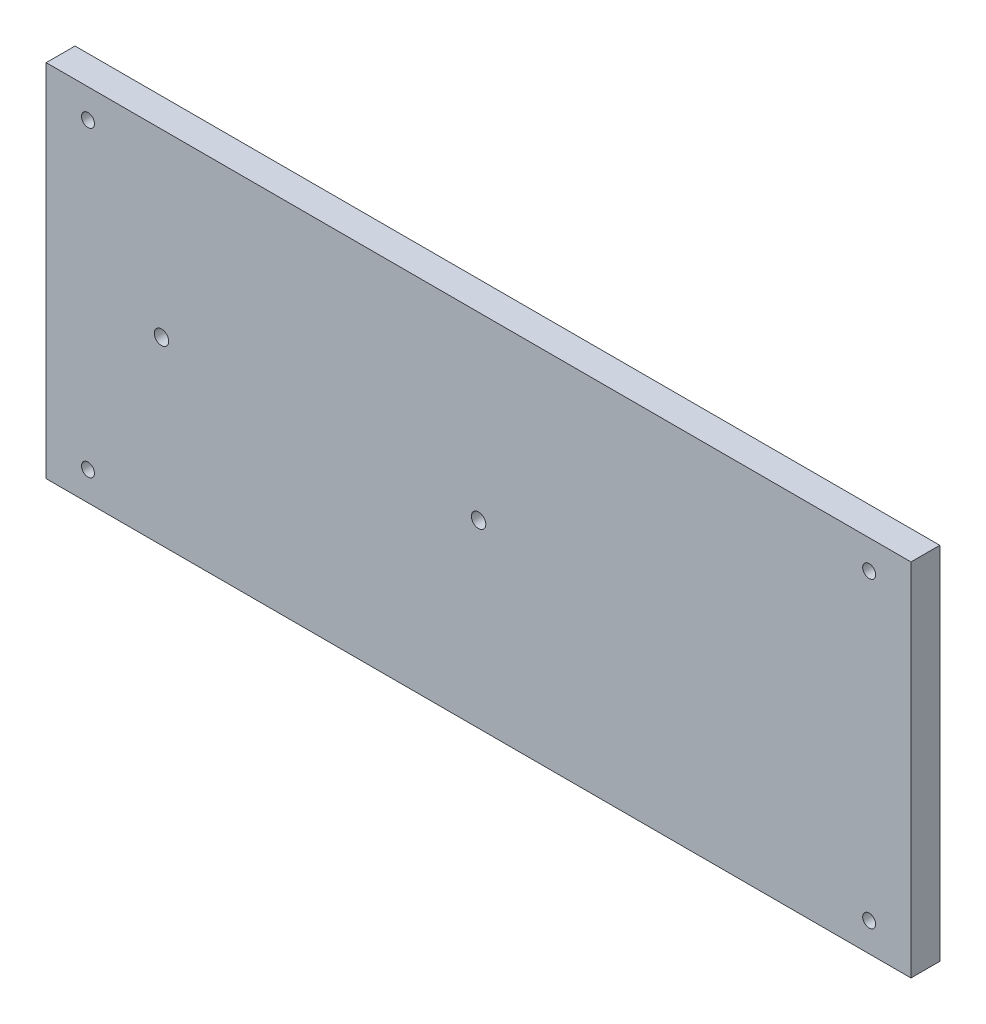
SolidWorks part; units mm, degrees
ref_plane "Plan de face" through (0, 0, 0) normal (0, 0, 1) x (1, 0, 0)
ref_plane "Plan de dessus" through (0, 0, 0) normal (0, 1, 0) x (1, 0, 0)
ref_plane "Plan de droite" through (0, 0, 0) normal (1, 0, 0) x (0, 0, -1)
sketch "Esquisse1" plane through (0, 0, 0) normal (0, 0, 1) x (1, 0, 0)
  line L1 (-122.4446, 41.9355) -> (177.5554, 41.9355)
  line L2 (-122.4446, 41.9355) -> (-122.4446, -83.0645)
  line L3 (-122.4446, -83.0645) -> (177.5554, -83.0645)
  line L4 (177.5554, 41.9355) -> (177.5554, -83.0645)
  dimension "D1" = 300
  dimension "D2" = 125
extrude "Boss.-Extru.1" add sketch "Esquisse1" along normal blind 10
sketch "Esquisse2" plane through (0, 0, 0) normal (0, 0, -1) x (-1, 0, 0)
  line L0 (-177.5554, -83.0645) -> (-177.5554, 41.9355) construction
  line L1 (122.4446, -83.0645) -> (-177.5554, -83.0645) construction
  line L2 (-177.5554, 41.9355) -> (122.4446, 41.9355) construction
  line L3 (122.4446, 41.9355) -> (122.4446, -83.0645) construction
  circle A0 centre (-163.0554, -73.0645) radius 2.25
  circle A1 centre (-163.0554, 31.9355) radius 2.25
  circle A2 centre (107.9446, 31.9355) radius 2.25
  circle A3 centre (107.9446, -73.0645) radius 2.25
  dimension "D1" = 4.5
  dimension "D2" = 4.5
  dimension "D3" = 4.5
  dimension "D4" = 4.5
  dimension "D6" = 10
  dimension "D11" = 14.5
  dimension "D5" = 14.5
  dimension "D7" = 10
  dimension "D8" = 14.5
  dimension "D9" = 10
  dimension "D10" = 14.5
  dimension "D12" = 10
extrude "Enlèv. mat.-Extru.1" cut sketch "Esquisse2" against normal blind 10
sketch "Esquisse3" plane through (0, 0, 0) normal (0, 0, -1) x (-1, 0, 0)
  line L0 (122.4446, 41.9355) -> (122.4446, -83.0645) construction
  line L2 (122.4446, -83.0645) -> (-177.5554, -83.0645) construction
  circle A0 centre (82.4446, -20.5645) radius 2.5
  circle A1 centre (-27.5554, -20.5645) radius 2.5
  dimension "D1" = 5
  dimension "D2" = 5
  dimension "D3" = 110
  dimension "D4" = 40
  dimension "D5" = 62.5
  dimension "D6" = 62.5
extrude "Enlèv. mat.-Extru.2" cut sketch "Esquisse3" against normal blind 10
